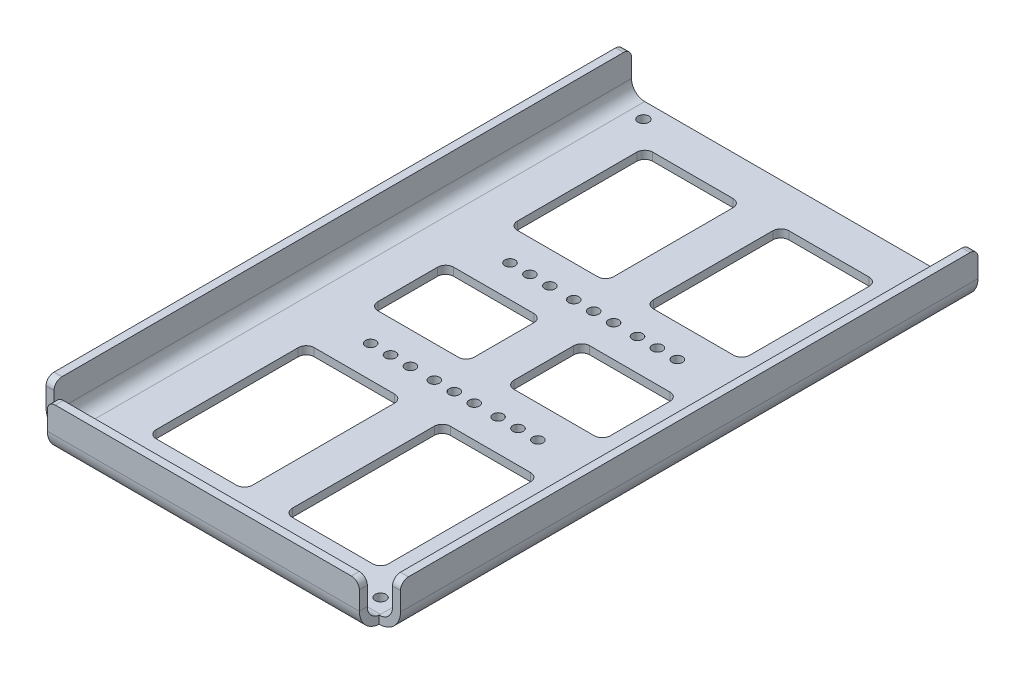
SolidWorks part; units mm, degrees
note: The reader was unsure of these and kept them because the rebuilt part matched: bend radius of "Base-Flange1", "BaseBend1", "BaseBend2"; flange length of "Edge-Flange1".
material "2024 Alloy (SN)"
ref_plane "Front Plane" through (0, 0, 0) normal (0, 0, 1) x (1, 0, 0)
ref_plane "Top Plane" through (0, 0, 0) normal (0, 1, 0) x (1, 0, 0)
ref_plane "Right Plane" through (0, 0, 0) normal (1, 0, 0) x (0, 0, -1)
sketch "Sketch1" plane through (0, 0, 0) normal (0, 0, 1) x (1, 0, 0)
  line L0 (-42.5, 10) -> (-42.5, 0)
  line L1 (-42.5, 0) -> (42.5, 0)
  line L2 (42.5, 0) -> (42.5, 10)
  point P2 (0, 0)
  dimension "D1" = 85
  dimension "D2" = 10
sheet metal parameters "Sheet-Metal1" thickness 2 parameters "D1"=3.33
base flange "Base-Flange1" sketch "Sketch1" end condition mid plane depth 150 reverse direction no thickness 2 reverse thickness direction no bend radius 3.33
bend "BaseBend1" bend radius 3.33 bend angle 90 parameters "D5"=1
bend "BaseBend2" bend radius 3.33 bend angle 90 parameters "D5"=2
sketch "Sketch5" plane through (0, 0, 0) normal (0, 1, 0) x (-1, 0, 0)
  line L0 (0, -30.2296) -> (0, 39.2801) construction
  circle A0 centre (0, -23) radius 1.3
  circle A1 centre (16, -23) radius 1.3
  circle A2 centre (16, 12) radius 1.3
  circle A3 centre (0, 12) radius 1.3
  circle A4 centre (-16, 12) radius 1.3
  circle A5 centre (-16, -23) radius 1.3
  circle A6 centre (11, 12) radius 1.3
  circle A7 centre (5, 12) radius 1.3
  circle A8 centre (-5, 12) radius 1.3
  circle A9 centre (-11, 12) radius 1.3
  circle A10 centre (11, -23) radius 1.3
  circle A11 centre (5, -23) radius 1.3
  circle A12 centre (-5, -23) radius 1.3
  circle A13 centre (-11, -23) radius 1.3
  circle A14 centre (21, 12) radius 1.3
  circle A15 centre (21, -23) radius 1.3
  circle A16 centre (-21, -23) radius 1.3
  circle A17 centre (-21, 12) radius 1.3
  dimension "D2" = 16
  dimension "D3" = 2.6
  dimension "D4" = 12
  dimension "D6" = 16
  dimension "D7" = 5
  dimension "D8" = 5
  dimension "D9" = 5
  dimension "D10" = 5
  dimension "D11" = 5
  dimension "D12" = 5
  dimension "D1" = 0
  dimension "D5" = 23
extrude "Cut-Extrude1" cut sketch "Sketch5" against normal blind 10 normal cut yes
sketch "Sketch6" plane through (0, -2, 0) normal (0, -1, 0) x (1, 0, 0)
  line L0 (44.5, 75) -> (44.5, -75) construction
  line L1 (-44.5, 75) -> (44.5, 75)
  line L2 (-44.5, 75) -> (-44.5, 70)
  line L3 (-44.5, 70) -> (44.5, 70)
  line L4 (44.5, 75) -> (44.5, 70)
  dimension "D1" = 5
extrude "Cut-Extrude2" cut sketch "Sketch6" against normal blind 35 normal cut yes
sketch "Sketch9" plane through (0, 0, 70) normal (0, 0, 1) x (1, 0, 0)
  line L1 (-39.17, 0) -> (39.17, 0)
  line L2 (-39.17, 0) -> (-39.17, -2)
  line L3 (-39.17, -2) -> (39.17, -2)
  line L4 (39.17, 0) -> (39.17, -2)
extrude "Boss-Extrude1" add sketch "Sketch9" along normal blind 3
edge flange "Edge-Flange1" sketch "Sketch12" flange angle 90 flange length 10 flange position material outside bend radius 3.33 thickness 2 relief none parameters "D6"=10
sketch "Sketch12" plane through (0, 0, 73) normal (0, 0, 1) x (1, 0, 0)
  line L0 (39.17, 0) -> (-39.17, 0) construction
  line L1 (39.17, 0) -> (-39.17, 0)
  line L2 (-39.17, 0) -> (-39.17, 10)
  line L3 (-39.17, 10) -> (39.17, 10)
  line L4 (39.17, 10) -> (39.17, 0)
bend "EdgeBend1" bend radius 3.33 bend angle 90 parameters "D5"=3
fillet "Fillet1" radius 2 6 edges at (-43.5, 10, -75) (43.5, 10, -75) (43.5, 10, 70) (39.17, 10, 74) (-43.5, 10, 70) (-39.17, 10, 74)
sketch "Sketch13" plane through (0, 0, 0) normal (0, 1, 0) x (1, 0, 0)
  line L0 (0, 59.9565) -> (0, -60.5843) construction
  line L1 (-39.17, -69.67) -> (-39.17, 75) construction
  line L2 (-29.17, 65) -> (-5, 65)
  line L3 (-29.17, 65) -> (-29.17, 31)
  line L4 (-29.17, 31) -> (-5, 31)
  line L5 (-5, 65) -> (-5, 31)
  line L6 (5, 65) -> (29.17, 65)
  line L7 (5, 65) -> (5, 31)
  line L8 (5, 31) -> (29.17, 31)
  line L9 (29.17, 65) -> (29.17, 31)
  line L10 (-29.17, 15) -> (-5, 15)
  line L11 (-29.17, 15) -> (-29.17, -4)
  line L12 (-29.17, -4) -> (-5, -4)
  line L13 (-5, 15) -> (-5, -4)
  line L14 (5, 15) -> (29.17, 15)
  line L15 (5, 15) -> (5, -4)
  line L16 (5, -4) -> (29.17, -4)
  line L17 (29.17, 15) -> (29.17, -4)
  line L18 (-29.17, -20) -> (-5, -20)
  line L19 (-29.17, -20) -> (-29.17, -59.67)
  line L20 (-29.17, -59.67) -> (-5, -59.67)
  line L21 (-5, -20) -> (-5, -59.67)
  line L22 (5, -20) -> (29.17, -20)
  line L23 (5, -20) -> (5, -59.67)
  line L24 (5, -59.67) -> (29.17, -59.67)
  line L25 (29.17, -20) -> (29.17, -59.67)
  line L26 (39.17, -69.67) -> (39.17, 75) construction
  line L27 (-39.17, 75) -> (39.17, 75) construction
  line L28 (39.17, -69.67) -> (-39.17, -69.67) construction
  circle A0 centre (-16, 23) radius 1.3 construction
  circle A1 centre (-11, 23) radius 1.3 construction
  circle A2 centre (-11, -12) radius 1.3 construction
  circle A3 centre (-16, -12) radius 1.3 construction
  dimension "D6" = 8
  dimension "D8" = 8
  dimension "D1" = 5
  dimension "D2" = 5
  dimension "D3" = 10
  dimension "D4" = 10
  dimension "D5" = 10
  dimension "D7" = 8
  dimension "D9" = 8
  dimension "D10" = 10
extrude "Cut-Extrude3" cut sketch "Sketch13" against normal blind 10 normal cut yes
fillet "Fillet2" radius 2 24 edges at (29.17, -1, 59.67) (-5, -1, 59.67) (-5, -1, 4) (29.17, -1, 4) (29.17, -1, -31) (-5, -1, -31) (5, -1, -31) (5, -1, 4) (5, -1, 59.67) (-29.17, -1, 59.67) (-29.17, -1, 4) (-29.17, -1, -31) (-29.17, -1, -15) (-29.17, -1, 20) (5, -1, 20) (5, -1, -15) (5, -1, -65) (29.17, -1, 20) (-5, -1, 20) (-5, -1, -15) (29.17, -1, -15) (29.17, -1, -65) (-5, -1, -65) (-29.17, -1, -65)
sketch "Sketch14" plane through (0, 0, 0) normal (0, 1, 0) x (1, 0, 0)
  line L0 (-39.17, 75) -> (39.17, 75) construction
  line L1 (-35.5, 71) -> (35.5, 71) construction
  line L2 (-35.5, 71) -> (-35.5, -66) construction
  line L3 (-35.5, -66) -> (35.5, -66) construction
  line L4 (35.5, 71) -> (35.5, -66) construction
  line L5 (-44.5, -68) -> (-44.5, 73) construction
  line L6 (44.5, -68) -> (44.5, 73) construction
  line L7 (37.17, -75) -> (-37.17, -75) construction
  circle A0 centre (-35.5, 71) radius 1.37
  circle A1 centre (35.5, 71) radius 1.37
  circle A2 centre (35.5, -66) radius 1.37
  circle A3 centre (-35.5, -66) radius 1.37
  dimension "D5" = 2.74
  dimension "D1" = 4
  dimension "D2" = 9
  dimension "D3" = 9
  dimension "D4" = 9
extrude "Cut-Extrude4" cut sketch "Sketch14" against normal blind 10 normal cut yes
flat pattern "Flat-Pattern1" [suppressed]
sketch "Bend-Lines1" plane through (0, 0, 0) normal (0, 1, 0) x (-1, 0, 0)
  line L0 (42.5708, 70) -> (42.5708, -75) construction
  line L1 (-42.5708, -75) -> (-42.5708, 70) construction
  line L2 (42.5708, 70) -> (42.5708, -75) construction
  line L3 (-42.5708, -75) -> (-42.5708, 70) construction
  line L4 (-39.17, 73.0708) -> (39.17, 73.0708) construction
  line L5 (-39.17, 73.0708) -> (39.17, 73.0708) construction
sketch3d "Bounding-Box1" [suppressed]
  line L0 (-95.1416, -149.9999, 0) -> (-95.1415, 8.1416, 0) construction
  line L1 (10.1415, -150, 0) -> (10.1416, 8.1415, 0) construction
  line L2 (-95.1416, -149.9999, 0) -> (10.1415, -150, 0) construction
  line L3 (-95.1415, 8.1416, 0) -> (10.1416, 8.1415, 0) construction
bend of the flat pattern "Flatten-<BaseBend1>1"
bend of the flat pattern "Flatten-<BaseBend2>1"
bend of the flat pattern "Flatten-<EdgeBend1>1"
